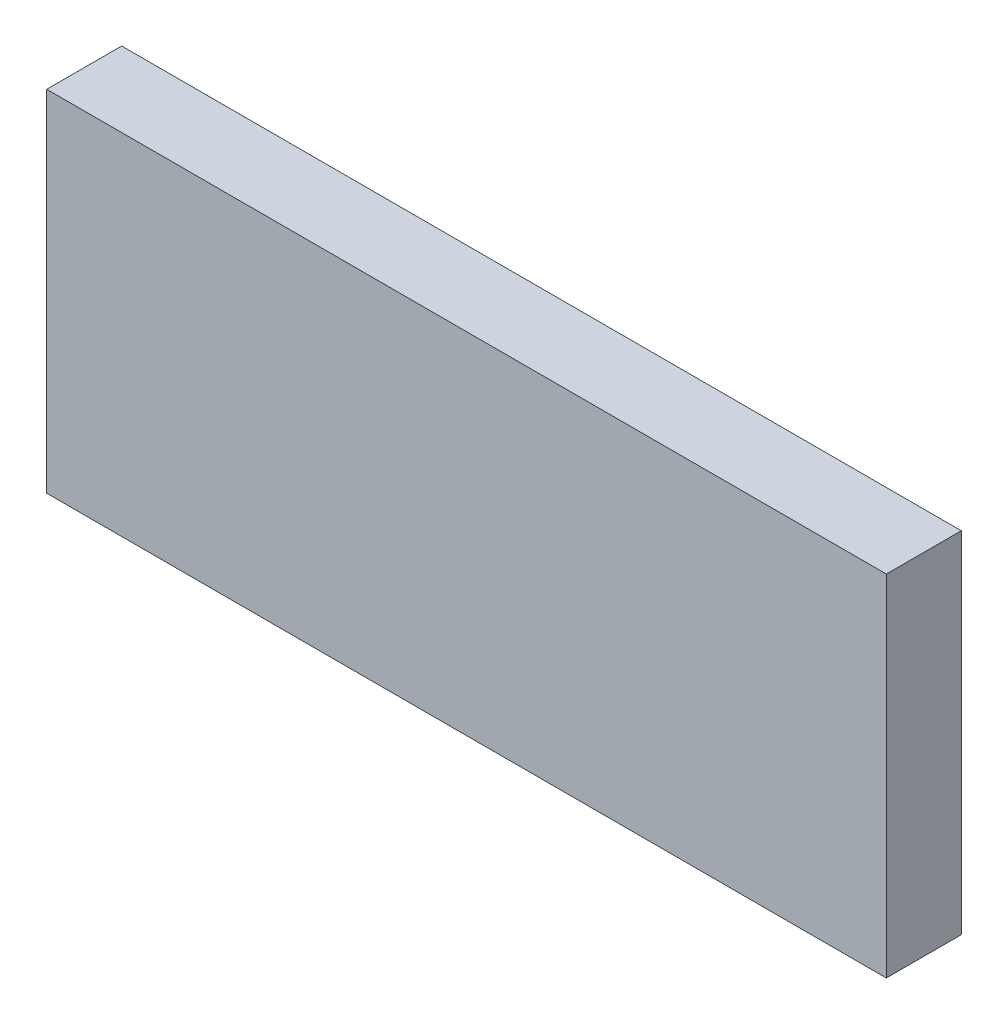
SolidWorks part; units mm, degrees
ref_plane "Front Plane" through (0, 0, 0) normal (0, 0, 1) x (1, 0, 0)
ref_plane "Top Plane" through (0, 0, 0) normal (0, 1, 0) x (1, 0, 0)
ref_plane "Right Plane" through (0, 0, 0) normal (1, 0, 0) x (0, 0, -1)
sketch "Sketch1" plane through (0, 0, 0) normal (0, 0, 1) x (1, 0, 0)
  line L1 (-53.34, -22.225) -> (53.34, -22.225)
  line L2 (-53.34, -22.225) -> (-53.34, 22.225)
  line L3 (-53.34, 22.225) -> (53.34, 22.225)
  line L4 (53.34, -22.225) -> (53.34, 22.225)
  line L5 (-53.34, -22.225) -> (53.34, 22.225) construction
  line L6 (-53.34, 22.225) -> (53.34, -22.225) construction
  point P0 (0, 0)
  dimension "D1" = 44.45
  dimension "D2" = 106.68
extrude "Boss-Extrude1" add sketch "Sketch1" along normal blind 9.525
